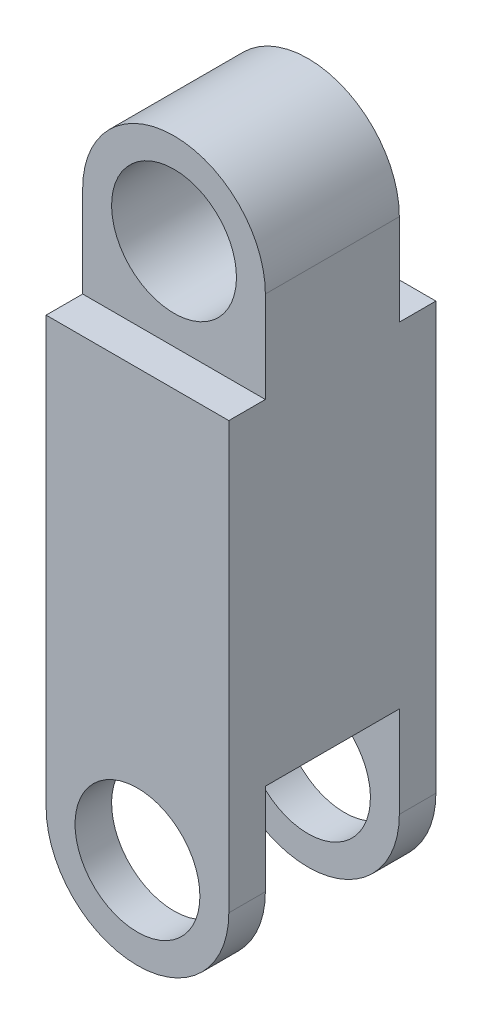
SolidWorks part; units mm, degrees
ref_plane "Front Plane" through (0, 0, 0) normal (0, 0, 1) x (1, 0, 0)
ref_plane "Top Plane" through (0, 0, 0) normal (0, 1, 0) x (1, 0, 0)
ref_plane "Right Plane" through (0, 0, 0) normal (1, 0, 0) x (0, 0, -1)
sketch "Sketch1" plane through (0, 0, 0) normal (0, 0, 1) x (1, 0, 0)
  line L0 (0, 0) -> (0, -85) construction
  line L5 (10.25, 0) -> (10.25, -85)
  line L6 (-10.25, 0) -> (-10.25, -85)
  line L7 (0, 0) -> (0, -85) construction
  line L8 (15, 0) -> (15, -85)
  line L9 (-15, 0) -> (-15, -85)
  arc A0 (10.25, 0) -> (-10.25, 0) centre (0, 0) ccw
  arc A1 (-10.25, -85) -> (10.25, -85) centre (0, -85) ccw
  arc A2 (15, 0) -> (-15, 0) centre (0, 0) ccw
  arc A3 (-15, -85) -> (15, -85) centre (0, -85) ccw
  circle A4 centre (0, 0) radius 10.25
  circle A5 centre (0, -85) radius 10.25
  point P2 (0, -42.5)
  point P11 (0, -42.5)
  dimension "D2" = 10.25
  dimension "D3" = 15
  dimension "D1" = 85
extrude "Boss-Extrude2" add sketch "Sketch1" along normal blind 34 contours L9 A3 L8 A2 A1 L6 A0 L5 | A5 L5 A4 L6 region at (0, -42.5, 0) region at (13.8115, -42.5, 0)
sketch "Sketch3" plane through (-15, 0, 0) normal (-1, 0, 0) x (0, 0, 1)
  line L1 (0, 15) -> (6, 15)
  line L2 (0, 15) -> (0, -15)
  line L3 (0, -15) -> (6, -15)
  line L4 (6, 15) -> (6, -15)
  line L5 (34, 15) -> (28, 15)
  line L6 (34, 15) -> (34, -15)
  line L7 (34, -15) -> (28, -15)
  line L8 (28, 15) -> (28, -15)
  line L10 (0, -42.5) -> (69.2504, -42.5) construction
  line L11 (0, 0) -> (0, -85) construction
  line L12 (28, -100) -> (28, -70)
  line L13 (34, -70) -> (28, -70)
  line L14 (34, -100) -> (34, -70)
  line L15 (34, -100) -> (28, -100)
  line L16 (6, -100) -> (6, -70)
  line L17 (0, -70) -> (6, -70)
  line L18 (0, -100) -> (0, -70)
  line L19 (0, -100) -> (6, -100)
  line L21 (6, -70) -> (28, -70)
  line L22 (6, -70) -> (6, -100)
  line L23 (6, -100) -> (28, -100)
  line L24 (28, -70) -> (28, -100)
  line M6 (0, 0) -> (0, -85)
  line M7 (0, -85) -> (34, -85)
  line M8 (34, -85) -> (34, 0)
  line M9 (34, 0) -> (0, 0)
  dimension "D1" = 6
  dimension "D2" = 6
  dimension "D3" = 30
extrude "Cut-Extrude3" cut sketch "Sketch3" against normal through all both and the other way through all contours L21 L16 L12 M7 | L16 L23 L12 M7 | L4 L3 M9 M6 | L8 L7 M9 M8 | L5 L8 L6 M9 | L4 L1 L2 M9 region at (-15, 7.5, 3) region at (-15, -7.5, 3) region at (-15, -7.5, 31) region at (-15, 7.5, 31) region at (-15, -77.5, 17) region at (-15, -92.5, 17)
